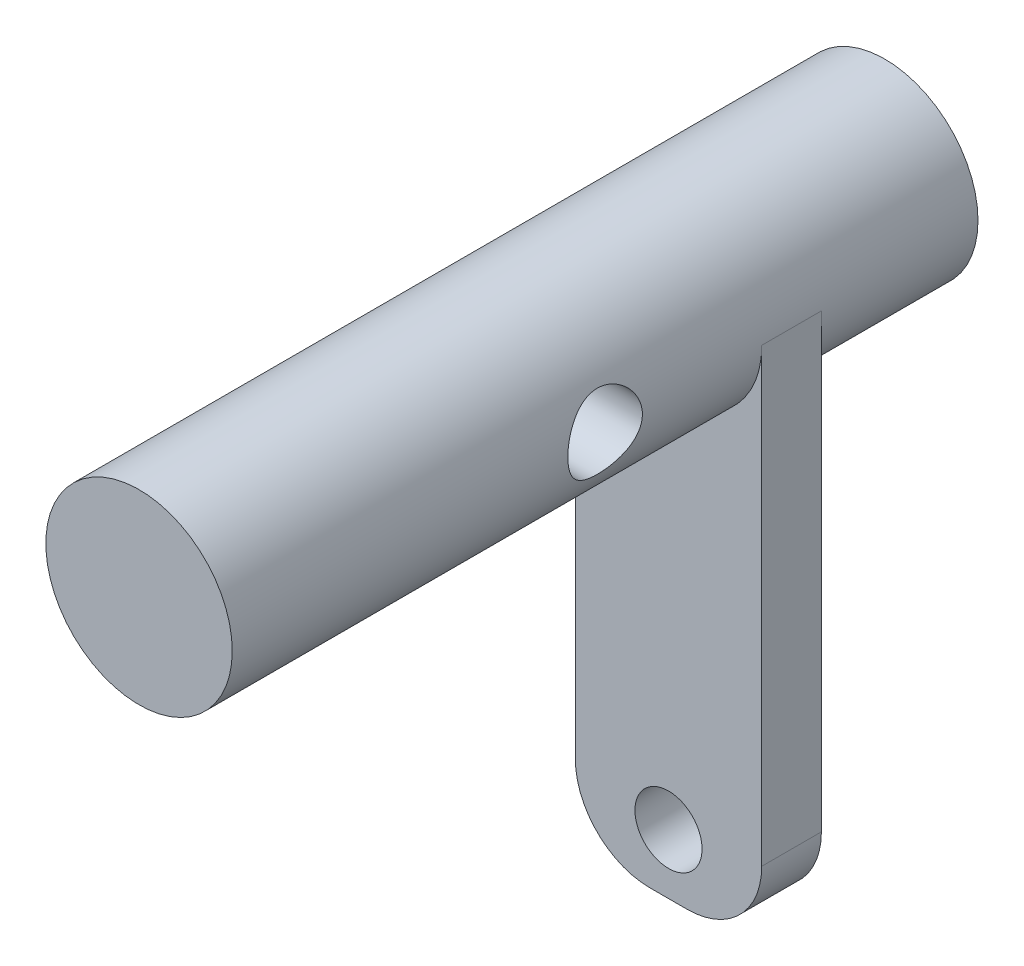
SolidWorks part; units mm, degrees
ref_plane "Płaszczyzna przednia" through (0, 0, 0) normal (0, 0, 1) x (1, 0, 0)
ref_plane "Płaszczyzna górna" through (0, 0, 0) normal (0, 1, 0) x (1, 0, 0)
ref_plane "Płaszczyzna prawa" through (0, 0, 0) normal (1, 0, 0) x (0, 0, -1)
sketch "Szkic1" plane through (0, 0, 0) normal (0, 0, 1) x (1, 0, 0)
  circle A0 centre (0, 0) radius 12.5
  dimension "D1" = 25
extrude "pręt" add sketch "Szkic1" along normal blind 100
ref_plane "Płaszczyzna otworu" through (12.5, 0, 0) normal (1, 0, 0) x (0, 0, -1)
sketch "Szkic2" plane through (12.5, 0, 0) normal (1, 0, 0) x (0, 0, -1)
  line L0 (0, -12.5) -> (0, 12.5) construction
  circle A0 centre (-50, 0) radius 5
  dimension "D2" = 10
  dimension "D1" = 50
extrude "otwór oś" cut sketch "Szkic2" against normal blind 100
ref_plane "Płaszczyzna pod drążek" through (0, -12.5, 0) normal (0, -1, 0) x (-1, 0, 0)
sketch "Szkic3" plane through (0, -12.5, 0) normal (0, -1, 0) x (-1, 0, 0)
  line L0 (12.5, -45) -> (12.5, 0) construction
  line L1 (-12.5, -29) -> (12.5, -29)
  line L2 (-12.5, -29) -> (-12.5, -21)
  line L3 (-12.5, -21) -> (12.5, -21)
  line L4 (12.5, -29) -> (12.5, -21)
  line L5 (-12.5, -29) -> (12.5, -21) construction
  line L6 (-12.5, -21) -> (12.5, -29) construction
  line L7 (-12.5, -100) -> (12.5, -100) construction
  point P0 (0, -25)
  dimension "D1" = 25
  dimension "D2" = 8
  dimension "D3" = 75
extrude "płaskownik pod drążek" add sketch "Szkic3" along normal blind 58 and the other way up to surface separate body other way up to face at (-12.479, 0.725, 45.0528)
sketch "Szkic4" plane through (0, 0, 21) normal (0, 0, -1) x (-1, 0, 0)
  line L1 (12.5, -70.5) -> (-12.5, -70.5) construction
  line L2 (12.5, -70.5) -> (12.5, 0) construction
  circle A1 centre (0, -62.5) radius 4.5
  dimension "D1" = 8
  dimension "D3" = 9
  dimension "D2" = 12.5
extrude "otwór na drążek" cut sketch "Szkic4" against normal up to next (8 mm away)
fillet "Zaokrąglenie płaskownik" radius 10 2 edges at (-12.5, -70.5, 25) (12.5, -70.5, 25)
